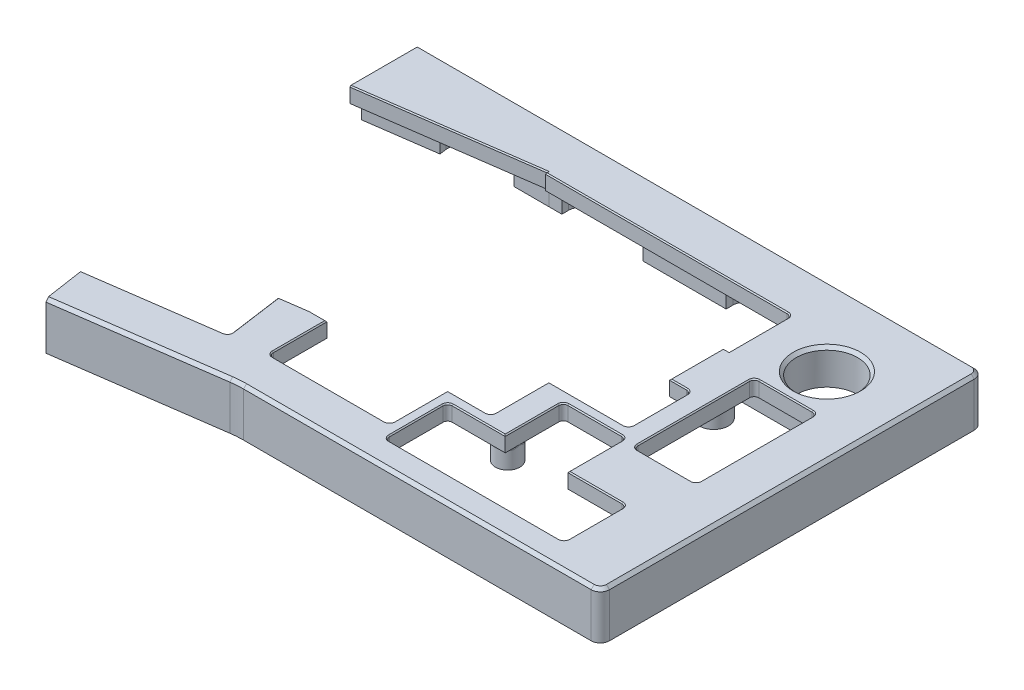
SolidWorks part; units mm, degrees
ref_plane "Front Plane" through (0, 0, 0) normal (0, 0, 1) x (1, 0, 0)
ref_plane "Top Plane" through (0, 0, 0) normal (0, 1, 0) x (1, 0, 0)
ref_plane "Right Plane" through (0, 0, 0) normal (1, 0, 0) x (0, 0, -1)
sketch "Sketch1" plane through (0, 7, 0) normal (0, 1, 0) x (1, 0, 0)
  line L0 (163.7923, 108.4551) -> (345.2139, 108.4551)
  line L1 (348.2139, 105.4551) -> (348.2139, -13.9968)
  line L2 (345.2139, -16.9968) -> (231.3639, -16.9968)
  line L3 (227.1887, -17.2887) -> (174.3706, -24.7118)
  line L4 (158.5745, -26.9318) -> (229.2661, -16.9968) construction
  line L5 (174.3706, -24.7118) -> (163.7923, 45.7292)
  line L6 (163.7923, 45.7292) -> (163.7923, 108.4551)
  line L7 (-20.6294, 108.4551) -> (-20.6294, -16.9968) construction
  line L12 (333.2139, 68.8908) -> (312.7139, 68.8908)
  line L13 (333.2139, 29.3396) -> (333.2139, 68.8908)
  line L14 (312.7139, 29.3396) -> (333.2139, 29.3396)
  line L15 (312.7139, 68.8908) -> (312.7139, 29.3396)
  line L16 (333.2139, 68.8908) -> (312.7139, 68.8908)
  line L17 (333.2139, 29.3396) -> (333.2139, 68.8908)
  line L18 (312.7139, 29.3396) -> (333.2139, 29.3396)
  line L19 (312.7139, 68.8908) -> (312.7139, 29.3396)
  line L24 (308.8285, 11.7372) -> (308.8285, 30.7884)
  line L25 (308.8285, 30.7884) -> (288.3285, 30.7884)
  line L26 (288.3285, 30.7884) -> (288.3285, 11.7372)
  line L27 (288.3285, 11.7372) -> (269.4673, 11.7372)
  line L28 (269.4673, 11.7372) -> (269.4673, -8.7628)
  line L29 (269.4673, -8.7628) -> (328.0696, -8.7628)
  line L30 (328.0696, -8.7628) -> (328.0696, 11.7372)
  line L31 (328.0696, 11.7372) -> (308.8285, 11.7372)
  line L32 (308.8285, 11.7372) -> (308.8285, 30.7884)
  line L33 (308.8285, 30.7884) -> (288.3285, 30.7884)
  line L34 (288.3285, 30.7884) -> (288.3285, 11.7372)
  line L35 (288.3285, 11.7372) -> (269.4673, 11.7372)
  line L36 (269.4673, 11.7372) -> (269.4673, -8.7628)
  line L37 (269.4673, -8.7628) -> (328.0696, -8.7628)
  line L38 (328.0696, -8.7628) -> (328.0696, 11.7372)
  line L39 (328.0696, 11.7372) -> (308.8285, 11.7372)
  line L59 (220.4901, 92.7047) -> (220.3983, 93.3575)
  line L60 (220.3983, 93.3575) -> (143.4989, 82.55)
  line L61 (143.4989, 82.55) -> (146.1495, 63.6897)
  line L62 (146.1495, 63.6897) -> (136.7192, 62.3644)
  line L63 (136.7192, 62.3644) -> (139.5722, 42.0639)
  line L64 (139.5722, 42.0639) -> (144.2882, 42.7267)
  line L65 (144.2882, 42.7267) -> (146.738, 25.2953)
  line L66 (146.738, 25.2953) -> (137.3043, 23.9695)
  line L67 (137.3043, 23.9695) -> (140.1573, 3.669)
  line L68 (140.1573, 3.669) -> (149.2141, 4.9418)
  line L69 (149.2141, 4.9418) -> (151.8663, -13.9296)
  line L70 (151.8663, -13.9296) -> (214.6125, -5.1112)
  line L71 (214.6125, -5.1112) -> (211.9605, 13.7588)
  line L72 (211.9605, 13.7588) -> (221.1558, 15.0512)
  line L73 (221.1558, 15.0512) -> (226.6027, 15.0512)
  line L74 (226.6027, 15.0512) -> (226.6027, -4)
  line L75 (226.6027, -4) -> (266.1519, -4)
  line L76 (266.1519, -4) -> (266.1519, 15.0512)
  line L77 (266.1519, 15.0512) -> (280.2517, 15.0512)
  line L78 (280.2517, 15.0512) -> (280.2517, 34.1024)
  line L79 (280.2517, 34.1024) -> (306.3508, 34.1024)
  line L80 (306.3508, 34.1024) -> (306.3508, 54.6024)
  line L81 (306.3508, 54.6024) -> (299.3029, 54.6024)
  line L82 (299.3029, 54.6024) -> (299.3029, 72.2047)
  line L83 (299.3029, 72.2047) -> (301.207, 72.2047)
  line L84 (301.207, 72.2047) -> (301.207, 92.7047)
  line L85 (301.207, 92.7047) -> (220.4901, 92.7047)
  line L86 (220.4901, 92.7047) -> (220.3983, 93.3575)
  line L87 (220.3983, 93.3575) -> (143.4989, 82.55)
  line L88 (143.4989, 82.55) -> (146.1495, 63.6897)
  line L89 (146.1495, 63.6897) -> (136.7192, 62.3644)
  line L90 (136.7192, 62.3644) -> (139.5722, 42.0639)
  line L91 (139.5722, 42.0639) -> (144.2882, 42.7267)
  line L92 (144.2882, 42.7267) -> (146.738, 25.2953)
  line L93 (146.738, 25.2953) -> (137.3043, 23.9695)
  line L94 (137.3043, 23.9695) -> (140.1573, 3.669)
  line L95 (140.1573, 3.669) -> (149.2141, 4.9418)
  line L96 (149.2141, 4.9418) -> (151.8663, -13.9296)
  line L97 (151.8663, -13.9296) -> (214.6125, -5.1112)
  line L98 (214.6125, -5.1112) -> (211.9605, 13.7588)
  line L99 (211.9605, 13.7588) -> (221.1558, 15.0512)
  line L100 (221.1558, 15.0512) -> (226.6027, 15.0512)
  line L101 (226.6027, 15.0512) -> (226.6027, -4)
  line L102 (226.6027, -4) -> (266.1519, -4)
  line L103 (266.1519, -4) -> (266.1519, 15.0512)
  line L104 (266.1519, 15.0512) -> (280.2517, 15.0512)
  line L105 (280.2517, 15.0512) -> (280.2517, 34.1024)
  line L106 (280.2517, 34.1024) -> (306.3508, 34.1024)
  line L107 (306.3508, 34.1024) -> (306.3508, 54.6024)
  line L108 (306.3508, 54.6024) -> (299.3029, 54.6024)
  line L109 (299.3029, 54.6024) -> (299.3029, 72.2047)
  line L110 (299.3029, 72.2047) -> (301.207, 72.2047)
  line L111 (301.207, 72.2047) -> (301.207, 92.7047)
  line L112 (301.207, 92.7047) -> (220.4901, 92.7047)
  arc A0 (348.2139, -13.9968) -> (345.2139, -16.9968) centre (345.2139, -13.9968) cw
  circle A1 centre (322.9639, 82.4547) radius 3.45
  circle A2 centre (322.9639, 82.4547) radius 3.45
  arc A3 (348.2139, 105.4551) -> (345.2139, 108.4551) centre (345.2139, 105.4551) ccw
  arc A4 (227.1887, -17.2887) -> (231.3639, -16.9968) centre (231.3639, -46.9968) cw
  point P4 (-20.6294, 45.7292)
  point P42 (348.2139, -16.9968)
  point P48 (348.2139, 108.4551)
  point P54 (229.2661, -16.9968)
  dimension "D5" = 3
  dimension "D6" = 30
  dimension "D1" = 0
  dimension "D2" = 0
  dimension "D3" = 0
  dimension "D4" = 0
extrude "Boss-Extrude1" add sketch "Sketch1" against normal offset from surface (5 mm away) 1 contours L3 A4 L2 A0 L1 A3 L0 L6 L87 L86 L112 L111 L110 L109 L108 L107 L106 L105 L104 L103 L102 L101 L100 L99 L98 L97 L5 L19 L16 L17 L18 L39 L38 L37 L36 L35 L34 L33 L32 A2 region at (254.5031, 7, -106.1803)
fillet "Fillet1" radius 1 7 edges at (200.7796, 7, 21.0003) (229.2712, 7, 17.0698) (288.2889, 7, 16.9968) (347.3353, 7, 16.1181) (348.2139, 7, -45.7292) (347.3353, 7, -107.5764) (254.5031, 7, -108.4551) profile chamfer
fillet "Fillet2" radius 1.5 17 edges at (301.207, 4.5, -92.7047) (312.7139, 4.5, -29.3396) (333.2139, 4.5, -29.3396) (333.2139, 4.5, -68.8908) (312.7139, 4.5, -68.8908) (306.3508, 4.5, -54.6024) (306.3508, 4.5, -34.1024) (280.2517, 4.5, -15.0512) (266.1519, 4.5, 4) (226.6027, 4.5, 4) (214.6125, 4.5, 5.1112) (269.4673, 4.5, 8.7628) (328.0696, 4.5, 8.7628) (328.0696, 4.5, -11.7372) (308.8285, 4.5, -30.7884) (288.3285, 4.5, -30.7884) (269.4673, 4.5, -11.7372)
sketch "Sketch2" plane through (0, 7, 0) normal (0, 1, 0) x (1, 0, 0)
  circle A1 centre (322.9639, 82.4547) radius 10.025
  circle A2 centre (322.9639, 82.4547) radius 10.025
  dimension "D1" = 0
extrude "Cut-Extrude1" cut sketch "Sketch2" against normal through all
chamfer "Chamfer1" distance 1 angle 45 1 edges at (322.9639, 7, -72.4297)
chamfer "Chamfer2" distance 0.35 angle 45 47 edges at (322.9639, 7, -29.3396) (332.7746, 7, -29.779) (313.1533, 7, -29.779) (333.2139, 7, -49.1152) (312.7139, 7, -49.1152) (332.7746, 7, -68.4514) (313.1533, 7, -68.4514) (322.9639, 7, -68.8908) (288.3285, 7, -20.5128) (288.7678, 7, -30.349) (298.5785, 7, -30.7884) (308.3891, 7, -30.349) (308.8285, 7, -20.5128) (279.6479, 7, -11.7372) (317.699, 7, -11.7372) (269.9066, 7, -11.2979) (327.6303, 7, -11.2979) (269.4673, 7, -1.4872) (328.0696, 7, -1.4872) (269.9066, 7, 8.3234) (327.6303, 7, 8.3234) (298.7685, 7, 8.7628) (192.7234, 7, 8.1876) (214.1163, 7, 4.7373) (213.1821, 7, -5.0665) (223.8793, 7, -15.0512) (216.5581, 7, -14.405) (226.6027, 7, -6.2756) (227.042, 7, 3.5607) (246.3773, 7, 4) (265.7125, 7, 3.5607) (266.1519, 7, -6.2756) (272.4518, 7, -15.0512) (279.8124, 7, -15.4905) (280.2517, 7, -25.3268) (292.5513, 7, -34.1024) (305.9115, 7, -34.5418) (306.3508, 7, -44.3524) (305.9115, 7, -54.1631) (302.0768, 7, -54.6024) (299.3029, 7, -63.4036) (300.2549, 7, -72.2047) (301.207, 7, -81.7047) (300.7676, 7, -92.2654) (260.0985, 7, -92.7047) (220.4442, 7, -93.0311) (192.0953, 7, -89.3798)
sketch "Sketch3" plane through (0, 2, 0) normal (0, -1, 0) x (1, 0, 0)
  line L0 (191.9476, 10.8212) -> (192.2607, 13.0493)
  line L1 (189.0691, 17.2847) -> (175.2054, 19.2331)
  line L9 (163.7923, -89.1482) -> (186.3819, -92.3229)
  line L10 (186.3819, -92.3229) -> (186.0687, -94.551)
  line L11 (189.2603, -98.7864) -> (203.1241, -100.7349)
  line L12 (207.3595, -97.5433) -> (207.6864, -95.2174)
  line L13 (207.6864, -95.2174) -> (219.1545, -95.2047)
  line L14 (219.1545, -95.2047) -> (223.4041, -95.2047)
  line L15 (223.4041, -95.2047) -> (223.4041, -97.4547)
  line L16 (227.1541, -101.2047) -> (246.1541, -101.2047)
  line L17 (249.9041, -97.4547) -> (249.9041, -95.2047)
  line L18 (249.9041, -95.2047) -> (277.207, -95.2047)
  line L19 (277.207, -95.2047) -> (277.207, -97.4547)
  line L20 (280.957, -101.2047) -> (299.957, -101.2047)
  line L21 (303.707, -97.4547) -> (303.707, -71.3908)
  line L22 (303.707, -71.3908) -> (330.2746, -71.3908)
  line L23 (330.2746, -71.3908) -> (335.2746, -66.3908)
  line L24 (174.3706, 24.7118) -> (172.3197, 11.0551)
  line L25 (172.3197, 11.0551) -> (213.1271, 5.32)
  line L26 (214.4037, 3.6258) -> (211.9605, -13.7588)
  line L27 (211.9605, -13.7588) -> (221.1558, -15.0512)
  line L28 (221.1558, -15.0512) -> (226.6027, -15.0512)
  line L29 (226.6027, -15.0512) -> (226.6027, 2.5)
  line L30 (228.1027, 4) -> (264.6519, 4)
  line L31 (266.1519, 2.5) -> (266.1519, -15.0512)
  line L32 (266.1519, -15.0512) -> (278.7517, -15.0512)
  line L33 (280.2517, -16.5512) -> (280.2517, -34.1024)
  line L34 (280.2517, -34.1024) -> (304.8508, -34.1024)
  line L35 (306.3508, -35.6024) -> (306.3508, -53.1024)
  line L36 (304.8508, -54.6024) -> (299.3029, -54.6024)
  line L37 (299.3029, -54.6024) -> (299.3029, -72.2047)
  line L38 (299.3029, -72.2047) -> (301.207, -72.2047)
  line L39 (301.207, -72.2047) -> (301.207, -91.2047)
  line L40 (299.707, -92.7047) -> (220.4901, -92.7047)
  line L41 (220.4901, -92.7047) -> (220.3983, -93.3575)
  line L42 (220.3983, -93.3575) -> (163.7923, -85.402)
  line L43 (163.7923, -85.402) -> (163.7923, -108.4551)
  line L44 (163.7923, -108.4551) -> (345.2139, -108.4551)
  line L45 (348.2139, -105.4551) -> (348.2139, 13.9968)
  line L46 (345.2139, 16.9968) -> (231.3639, 16.9968)
  line L47 (227.1887, 17.2887) -> (174.3706, 24.7118)
  line L68 (163.7923, -108.4551) -> (345.2139, -108.4551)
  line L69 (348.2139, -105.4551) -> (348.2139, 13.9968)
  line L70 (345.2139, 16.9968) -> (231.3639, 16.9968)
  line L71 (227.1887, 17.2887) -> (174.3706, 24.7118)
  line L72 (335.2746, -66.3908) -> (337.9639, -66.3908)
  line L73 (341.7139, -62.6408) -> (341.7139, -48.6408)
  line L74 (337.9639, -44.8908) -> (335.7139, -44.8908)
  line L75 (335.7139, -44.8908) -> (335.7139, -24.2372)
  line L76 (335.7139, -24.2372) -> (337.9639, -24.2372)
  line L77 (341.7139, -20.4872) -> (341.7139, -6.4872)
  line L78 (337.9639, -2.7372) -> (335.7139, -2.7372)
  line L79 (335.7139, -2.7372) -> (335.7139, 3.8234)
  line L80 (335.7139, 3.8234) -> (330.2746, 9.2628)
  line L81 (330.2746, 9.2628) -> (323.7139, 9.2628)
  line L82 (323.7139, 9.2628) -> (323.7139, 11.5128)
  line L83 (319.9639, 15.2628) -> (300.9639, 15.2628)
  line L84 (297.2139, 11.5128) -> (297.2139, 9.2628)
  line L85 (297.2139, 9.2628) -> (263.7139, 9.2628)
  line L86 (263.7139, 9.2628) -> (263.7139, 11.5128)
  line L87 (259.9639, 15.2628) -> (240.9639, 15.2628)
  line L88 (237.2139, 11.5128) -> (237.2139, 9.2628)
  line L89 (237.2139, 9.2628) -> (203.0362, 9.2628)
  line L90 (203.0362, 9.2628) -> (191.9476, 10.8212)
  line L91 (136.5182, 13.8474) -> (136.5182, -32.8206)
  line L92 (136.5182, -43.3206) -> (136.5182, -90.6166)
  line L93 (136.5182, -90.6166) -> (158.3041, -93.6785)
  line L94 (161.6924, -91.1252) -> (162.1099, -88.1544)
  line L95 (162.1099, -88.1544) -> (187.229, -91.6846)
  line L96 (187.229, -91.6846) -> (186.8114, -94.6554)
  line L97 (189.3647, -98.0437) -> (203.2285, -99.9922)
  line L98 (206.6168, -97.4389) -> (207.0343, -94.4681)
  line L99 (207.0343, -94.4681) -> (219.1541, -94.4547)
  line L100 (219.1541, -94.4547) -> (224.1541, -94.4547)
  line L101 (224.1541, -94.4547) -> (224.1541, -97.4547)
  line L102 (227.1541, -100.4547) -> (246.1541, -100.4547)
  line L103 (249.1541, -97.4547) -> (249.1541, -94.4547)
  line L104 (249.1541, -94.4547) -> (277.957, -94.4547)
  line L105 (277.957, -94.4547) -> (277.957, -97.4547)
  line L106 (280.957, -100.4547) -> (299.957, -100.4547)
  line L107 (302.957, -97.4547) -> (302.957, -70.6408)
  line L108 (302.957, -70.6408) -> (329.9639, -70.6408)
  line L109 (329.9639, -70.6408) -> (334.9639, -65.6408)
  line L110 (334.9639, -65.6408) -> (337.9639, -65.6408)
  line L111 (340.9639, -62.6408) -> (340.9639, -48.6408)
  line L112 (337.9639, -45.6408) -> (334.9639, -45.6408)
  line L113 (334.9639, -45.6408) -> (334.9639, -23.4872)
  line L114 (334.9639, -23.4872) -> (337.9639, -23.4872)
  line L115 (340.9639, -20.4872) -> (340.9639, -6.4872)
  line L116 (337.9639, -3.4872) -> (334.9639, -3.4872)
  line L117 (334.9639, -3.4872) -> (334.9639, 3.5128)
  line L118 (334.9639, 3.5128) -> (329.9639, 8.5128)
  line L119 (329.9639, 8.5128) -> (322.9639, 8.5128)
  line L120 (322.9639, 8.5128) -> (322.9639, 11.5128)
  line L121 (319.9639, 14.5128) -> (300.9639, 14.5128)
  line L122 (297.9639, 11.5128) -> (297.9639, 8.5128)
  line L123 (297.9639, 8.5128) -> (262.9639, 8.5128)
  line L124 (262.9639, 8.5128) -> (262.9639, 11.5128)
  line L125 (259.9639, 14.5128) -> (240.9639, 14.5128)
  line L126 (237.9639, 11.5128) -> (237.9639, 8.5128)
  line L127 (237.9639, 8.5128) -> (202.9837, 8.5128)
  line L128 (202.9837, 8.5128) -> (191.1005, 10.1828)
  line L129 (191.1005, 10.1828) -> (191.518, 13.1536)
  line L130 (188.9647, 16.542) -> (175.101, 18.4904)
  line L131 (171.7127, 15.9371) -> (171.2951, 12.9663)
  line L132 (171.2951, 12.9663) -> (165.0257, 13.8474)
  line L133 (165.0257, 13.8474) -> (136.5182, 13.8474)
  line L137 (161.6924, -91.1252) -> (162.1099, -88.1544) construction
  line L138 (162.1099, -88.1544) -> (187.229, -91.6846) construction
  line L139 (187.229, -91.6846) -> (186.8114, -94.6554) construction
  line L140 (189.3647, -98.0437) -> (203.2285, -99.9922) construction
  line L141 (206.6168, -97.4389) -> (207.0343, -94.4681) construction
  line L142 (207.0343, -94.4681) -> (219.1541, -94.4547) construction
  line L143 (219.1541, -94.4547) -> (224.1541, -94.4547) construction
  line L144 (224.1541, -94.4547) -> (224.1541, -97.4547) construction
  line L145 (227.1541, -100.4547) -> (246.1541, -100.4547) construction
  line L146 (249.1541, -97.4547) -> (249.1541, -94.4547) construction
  line L147 (249.1541, -94.4547) -> (277.957, -94.4547) construction
  line L148 (277.957, -94.4547) -> (277.957, -97.4547) construction
  line L149 (280.957, -100.4547) -> (299.957, -100.4547) construction
  line L150 (302.957, -97.4547) -> (302.957, -70.6408) construction
  line L151 (302.957, -70.6408) -> (329.9639, -70.6408) construction
  line L152 (329.9639, -70.6408) -> (334.9639, -65.6408) construction
  line L153 (334.9639, -65.6408) -> (337.9639, -65.6408) construction
  line L154 (340.9639, -62.6408) -> (340.9639, -48.6408) construction
  line L155 (337.9639, -45.6408) -> (334.9639, -45.6408) construction
  line L156 (334.9639, -45.6408) -> (334.9639, -23.4872) construction
  line L157 (334.9639, -23.4872) -> (337.9639, -23.4872) construction
  line L158 (340.9639, -20.4872) -> (340.9639, -6.4872) construction
  line L159 (337.9639, -3.4872) -> (334.9639, -3.4872) construction
  line L160 (334.9639, -3.4872) -> (334.9639, 3.5128) construction
  line L161 (334.9639, 3.5128) -> (329.9639, 8.5128) construction
  line L162 (329.9639, 8.5128) -> (322.9639, 8.5128) construction
  line L163 (322.9639, 8.5128) -> (322.9639, 11.5128) construction
  line L164 (319.9639, 14.5128) -> (300.9639, 14.5128) construction
  line L165 (297.9639, 11.5128) -> (297.9639, 8.5128) construction
  line L166 (297.9639, 8.5128) -> (262.9639, 8.5128) construction
  line L167 (262.9639, 8.5128) -> (262.9639, 11.5128) construction
  line L168 (259.9639, 14.5128) -> (240.9639, 14.5128) construction
  line L169 (237.9639, 11.5128) -> (237.9639, 8.5128) construction
  line L170 (237.9639, 8.5128) -> (202.9837, 8.5128) construction
  line L171 (202.9837, 8.5128) -> (191.1005, 10.1828) construction
  line L172 (191.1005, 10.1828) -> (191.518, 13.1536)
  line L173 (188.9647, 16.542) -> (175.101, 18.4904) construction
  line L174 (171.7127, 15.9371) -> (171.2951, 12.9663) construction
  line L175 (171.2951, 12.9663) -> (165.0257, 13.8474) construction
  line L177 (165.0782, 14.5974) -> (135.7682, 14.5974) construction
  line L178 (135.7682, 14.5974) -> (135.7682, -33.6335) construction
  line L179 (135.7682, -42.5076) -> (135.7682, -91.2686) construction
  line L180 (135.7682, -91.2686) -> (158.1997, -94.4212) construction
  line L181 (136.5182, 13.8474) -> (136.5182, -32.8206) construction
  line L182 (136.5182, -43.3206) -> (136.5182, -90.6166) construction
  line L183 (136.5182, -90.6166) -> (158.3041, -93.6785) construction
  line L184 (165.0257, 13.8474) -> (136.5182, 13.8474) construction
  line L185 (163.7923, -108.4551) -> (163.7923, -89.1482)
  line L186 (163.7923, -108.4551) -> (163.7923, -85.402) construction
  line L187 (174.3706, 24.7118) -> (173.5258, 19.0864)
  line L188 (162.4351, -91.2296) -> (162.7483, -89.0014) construction
  line L189 (162.7483, -89.0014) -> (186.3819, -92.3229) construction
  line L190 (172.3197, 11.0551) -> (174.3706, 24.7118) construction
  line L192 (170.97, 16.0415) -> (170.6568, 13.8134) construction
  line L193 (170.6568, 13.8134) -> (165.0782, 14.5974) construction
  arc A0 (192.2607, 13.0493) -> (189.0691, 17.2847) centre (188.5472, 13.5712) ccw
  arc A1 (175.2054, 19.2331) -> (173.5258, 19.0864) centre (174.6835, 15.5196) ccw
  arc A4 (186.0687, -94.551) -> (189.2603, -98.7864) centre (189.7822, -95.0729) ccw
  arc A5 (203.1241, -100.7349) -> (207.3595, -97.5433) centre (203.646, -97.0214) ccw
  arc A6 (223.4041, -97.4547) -> (227.1541, -101.2047) centre (227.1541, -97.4547) ccw
  arc A7 (246.1541, -101.2047) -> (249.9041, -97.4547) centre (246.1541, -97.4547) ccw
  arc A8 (277.207, -97.4547) -> (280.957, -101.2047) centre (280.957, -97.4547) ccw
  arc A9 (299.957, -101.2047) -> (303.707, -97.4547) centre (299.957, -97.4547) ccw
  arc A10 (214.4037, 3.6258) -> (213.1271, 5.32) centre (212.9183, 3.8346) ccw
  arc A11 (228.1027, 4) -> (226.6027, 2.5) centre (228.1027, 2.5) ccw
  arc A12 (266.1519, 2.5) -> (264.6519, 4) centre (264.6519, 2.5) ccw
  arc A13 (280.2517, -16.5512) -> (278.7517, -15.0512) centre (278.7517, -16.5512) ccw
  arc A14 (306.3508, -35.6024) -> (304.8508, -34.1024) centre (304.8508, -35.6024) ccw
  arc A15 (304.8508, -54.6024) -> (306.3508, -53.1024) centre (304.8508, -53.1024) ccw
  arc A16 (299.707, -92.7047) -> (301.207, -91.2047) centre (299.707, -91.2047) ccw
  arc A17 (345.2139, -108.4551) -> (348.2139, -105.4551) centre (345.2139, -105.4551) ccw
  arc A18 (348.2139, 13.9968) -> (345.2139, 16.9968) centre (345.2139, 13.9968) ccw
  arc A19 (227.1887, 17.2887) -> (231.3639, 16.9968) centre (231.3639, 46.9968) ccw
  arc A27 (345.2139, -108.4551) -> (348.2139, -105.4551) centre (345.2139, -105.4551) ccw
  arc A28 (348.2139, 13.9968) -> (345.2139, 16.9968) centre (345.2139, 13.9968) ccw
  arc A29 (227.1887, 17.2887) -> (231.3639, 16.9968) centre (231.3639, 46.9968) ccw
  arc A30 (337.9639, -66.3908) -> (341.7139, -62.6408) centre (337.9639, -62.6408) ccw
  arc A31 (341.7139, -48.6408) -> (337.9639, -44.8908) centre (337.9639, -48.6408) ccw
  arc A32 (337.9639, -24.2372) -> (341.7139, -20.4872) centre (337.9639, -20.4872) ccw
  arc A33 (341.7139, -6.4872) -> (337.9639, -2.7372) centre (337.9639, -6.4872) ccw
  arc A34 (323.7139, 11.5128) -> (319.9639, 15.2628) centre (319.9639, 11.5128) ccw
  arc A35 (300.9639, 15.2628) -> (297.2139, 11.5128) centre (300.9639, 11.5128) ccw
  arc A36 (263.7139, 11.5128) -> (259.9639, 15.2628) centre (259.9639, 11.5128) ccw
  arc A37 (240.9639, 15.2628) -> (237.2139, 11.5128) centre (240.9639, 11.5128) ccw
  arc A38 (136.5182, -43.3206) -> (136.5182, -32.8206) centre (136.5182, -38.0706) ccw
  arc A39 (158.3041, -93.6785) -> (161.6924, -91.1252) centre (158.7216, -90.7077) ccw
  arc A40 (186.8114, -94.6554) -> (189.3647, -98.0437) centre (189.7822, -95.0729) ccw
  arc A41 (203.2285, -99.9922) -> (206.6168, -97.4389) centre (203.646, -97.0214) ccw
  arc A42 (224.1541, -97.4547) -> (227.1541, -100.4547) centre (227.1541, -97.4547) ccw
  arc A43 (246.1541, -100.4547) -> (249.1541, -97.4547) centre (246.1541, -97.4547) ccw
  arc A44 (277.957, -97.4547) -> (280.957, -100.4547) centre (280.957, -97.4547) ccw
  arc A45 (299.957, -100.4547) -> (302.957, -97.4547) centre (299.957, -97.4547) ccw
  arc A46 (337.9639, -65.6408) -> (340.9639, -62.6408) centre (337.9639, -62.6408) ccw
  arc A47 (340.9639, -48.6408) -> (337.9639, -45.6408) centre (337.9639, -48.6408) ccw
  arc A48 (337.9639, -23.4872) -> (340.9639, -20.4872) centre (337.9639, -20.4872) ccw
  arc A49 (340.9639, -6.4872) -> (337.9639, -3.4872) centre (337.9639, -6.4872) ccw
  arc A50 (322.9639, 11.5128) -> (319.9639, 14.5128) centre (319.9639, 11.5128) ccw
  arc A51 (300.9639, 14.5128) -> (297.9639, 11.5128) centre (300.9639, 11.5128) ccw
  arc A52 (262.9639, 11.5128) -> (259.9639, 14.5128) centre (259.9639, 11.5128) ccw
  arc A53 (240.9639, 14.5128) -> (237.9639, 11.5128) centre (240.9639, 11.5128) ccw
  arc A54 (191.518, 13.1536) -> (188.9647, 16.542) centre (188.5472, 13.5712) ccw
  arc A55 (175.101, 18.4904) -> (171.7127, 15.9371) centre (174.6835, 15.5196) ccw
  arc A58 (186.8114, -94.6554) -> (189.3647, -98.0437) centre (189.7822, -95.0729) ccw construction
  arc A59 (203.2285, -99.9922) -> (206.6168, -97.4389) centre (203.646, -97.0214) ccw construction
  arc A60 (224.1541, -97.4547) -> (227.1541, -100.4547) centre (227.1541, -97.4547) ccw construction
  arc A61 (246.1541, -100.4547) -> (249.1541, -97.4547) centre (246.1541, -97.4547) ccw construction
  arc A62 (277.957, -97.4547) -> (280.957, -100.4547) centre (280.957, -97.4547) ccw construction
  arc A63 (299.957, -100.4547) -> (302.957, -97.4547) centre (299.957, -97.4547) ccw construction
  arc A64 (337.9639, -65.6408) -> (340.9639, -62.6408) centre (337.9639, -62.6408) ccw construction
  arc A65 (340.9639, -48.6408) -> (337.9639, -45.6408) centre (337.9639, -48.6408) ccw construction
  arc A66 (337.9639, -23.4872) -> (340.9639, -20.4872) centre (337.9639, -20.4872) ccw construction
  arc A67 (340.9639, -6.4872) -> (337.9639, -3.4872) centre (337.9639, -6.4872) ccw construction
  arc A68 (322.9639, 11.5128) -> (319.9639, 14.5128) centre (319.9639, 11.5128) ccw construction
  arc A69 (300.9639, 14.5128) -> (297.9639, 11.5128) centre (300.9639, 11.5128) ccw construction
  arc A70 (262.9639, 11.5128) -> (259.9639, 14.5128) centre (259.9639, 11.5128) ccw construction
  arc A71 (240.9639, 14.5128) -> (237.9639, 11.5128) centre (240.9639, 11.5128) ccw construction
  arc A72 (191.518, 13.1536) -> (188.9647, 16.542) centre (188.5472, 13.5712) ccw construction
  arc A73 (175.101, 18.4904) -> (171.7127, 15.9371) centre (174.6835, 15.5196) ccw construction
  arc A74 (135.7682, -42.5076) -> (135.7682, -33.6335) centre (136.5182, -38.0706) ccw construction
  arc A75 (158.1997, -94.4212) -> (162.4351, -91.2296) centre (158.7216, -90.7077) ccw construction
  arc A76 (136.5182, -43.3206) -> (136.5182, -32.8206) centre (136.5182, -38.0706) ccw construction
  arc A77 (158.3041, -93.6785) -> (161.6924, -91.1252) centre (158.7216, -90.7077) ccw construction
  circle A78 centre (322.9639, -82.4547) radius 10.025
  arc A79 (175.2054, 19.2331) -> (170.97, 16.0415) centre (174.6835, 15.5196) ccw construction
  dimension "D1" = 0
  dimension "D2" = 0
  dimension "D3" = 0.75
extrude "Boss-Extrude2" add sketch "Sketch3" along normal up to surface (6.5 mm away) contours A37 L87 A36 L86 L85 L84 A35 L83 A34 L82 L81 L80 L79 L78 A33 L77 A32 L76 L75 L74 A31 L73 A30 L72 L23 L22 L21 A9 L20 A8 L19 L18 L17 A7 L16 A6 L15 L14 L13 L12 A5 L11 A4 L10 L9 L185 L68 A27 L69 A28 L70 region at (194.3568, 2, 11.6186)
sketch "Sketch4" plane through (0, -4.5, 0) normal (0, -1, 0) x (1, 0, 0)
  line L0 (163.7923, -104.4551) -> (344.2139, -104.4551)
  line L1 (344.2139, -104.4551) -> (344.2139, 12.9968)
  line L2 (344.2139, 12.9968) -> (231.3639, 12.9968)
  line L3 (226.632, 13.3276) -> (173.8139, 20.7507)
  line L5 (163.7923, -104.4551) -> (163.7923, -108.4551)
  line L6 (174.3706, 24.7118) -> (173.7765, 20.756)
  line L7 (174.3706, 24.7118) -> (173.5258, 19.0864) construction
  line L8 (173.8139, 20.7507) -> (173.7765, 20.756)
  line L42 (240.9639, 15.2628) -> (259.9639, 15.2628)
  line L43 (263.7139, 11.5128) -> (263.7139, 9.2628)
  line L44 (263.7139, 9.2628) -> (297.2139, 9.2628)
  line L45 (297.2139, 9.2628) -> (297.2139, 11.5128)
  line L46 (300.9639, 15.2628) -> (319.9639, 15.2628)
  line L47 (323.7139, 11.5128) -> (323.7139, 9.2628)
  line L48 (323.7139, 9.2628) -> (330.2746, 9.2628)
  line L49 (330.2746, 9.2628) -> (335.7139, 3.8234)
  line L50 (335.7139, 3.8234) -> (335.7139, -2.7372)
  line L51 (335.7139, -2.7372) -> (337.9639, -2.7372)
  line L52 (341.7139, -6.4872) -> (341.7139, -20.4872)
  line L53 (337.9639, -24.2372) -> (335.7139, -24.2372)
  line L54 (335.7139, -24.2372) -> (335.7139, -44.8908)
  line L55 (335.7139, -44.8908) -> (337.9639, -44.8908)
  line L56 (341.7139, -48.6408) -> (341.7139, -62.6408)
  line L57 (337.9639, -66.3908) -> (335.2746, -66.3908)
  line L58 (335.2746, -66.3908) -> (330.2746, -71.3908)
  line L59 (330.2746, -71.3908) -> (303.707, -71.3908)
  line L60 (303.707, -71.3908) -> (303.707, -97.4547)
  line L61 (299.957, -101.2047) -> (280.957, -101.2047)
  line L62 (277.207, -97.4547) -> (277.207, -95.2047)
  line L63 (277.207, -95.2047) -> (249.9041, -95.2047)
  line L64 (249.9041, -95.2047) -> (249.9041, -97.4547)
  line L65 (246.1541, -101.2047) -> (227.1541, -101.2047)
  line L66 (223.4041, -97.4547) -> (223.4041, -95.2047)
  line L67 (223.4041, -95.2047) -> (219.1545, -95.2047)
  line L68 (219.1545, -95.2047) -> (207.6864, -95.2174)
  line L69 (207.6864, -95.2174) -> (207.3595, -97.5433)
  line L70 (203.1241, -100.7349) -> (189.2603, -98.7864)
  line L71 (186.0687, -94.551) -> (186.3819, -92.3229)
  line L72 (186.3819, -92.3229) -> (163.7923, -89.1482)
  line L73 (163.7923, -89.1482) -> (163.7923, -108.4551)
  line L74 (163.7923, -108.4551) -> (345.2139, -108.4551)
  line L75 (348.2139, -105.4551) -> (348.2139, 13.9968)
  line L76 (345.2139, 16.9968) -> (231.3639, 16.9968)
  line L77 (227.1887, 17.2887) -> (174.3706, 24.7118)
  line L78 (174.3706, 24.7118) -> (173.5258, 19.0864)
  line L79 (175.2054, 19.2331) -> (189.0691, 17.2847)
  line L80 (192.2607, 13.0493) -> (191.9476, 10.8212)
  line L81 (191.9476, 10.8212) -> (203.0362, 9.2628)
  line L82 (203.0362, 9.2628) -> (237.2139, 9.2628)
  line L83 (237.2139, 9.2628) -> (237.2139, 11.5128)
  line L116 (163.7923, -108.4551) -> (345.2139, -108.4551)
  line L117 (348.2139, -105.4551) -> (348.2139, 13.9968)
  line L118 (345.2139, 16.9968) -> (231.3639, 16.9968)
  line L119 (227.1887, 17.2887) -> (174.3706, 24.7118)
  arc A1 (344.2139, -104.4551) -> (344.2139, -104.4551) centre (344.2139, -104.4551) ccw
  arc A2 (344.2139, 12.9968) -> (344.2139, 12.9968) centre (344.2139, 12.9968) ccw
  arc A3 (226.632, 13.3276) -> (231.3639, 12.9968) centre (231.3639, 46.9968) ccw
  arc A19 (240.9639, 15.2628) -> (237.2139, 11.5128) centre (240.9639, 11.5128) ccw
  arc A20 (263.7139, 11.5128) -> (259.9639, 15.2628) centre (259.9639, 11.5128) ccw
  arc A21 (300.9639, 15.2628) -> (297.2139, 11.5128) centre (300.9639, 11.5128) ccw
  arc A22 (323.7139, 11.5128) -> (319.9639, 15.2628) centre (319.9639, 11.5128) ccw
  arc A23 (341.7139, -6.4872) -> (337.9639, -2.7372) centre (337.9639, -6.4872) ccw
  arc A24 (337.9639, -24.2372) -> (341.7139, -20.4872) centre (337.9639, -20.4872) ccw
  arc A25 (341.7139, -48.6408) -> (337.9639, -44.8908) centre (337.9639, -48.6408) ccw
  arc A26 (337.9639, -66.3908) -> (341.7139, -62.6408) centre (337.9639, -62.6408) ccw
  arc A27 (299.957, -101.2047) -> (303.707, -97.4547) centre (299.957, -97.4547) ccw
  arc A28 (277.207, -97.4547) -> (280.957, -101.2047) centre (280.957, -97.4547) ccw
  arc A29 (246.1541, -101.2047) -> (249.9041, -97.4547) centre (246.1541, -97.4547) ccw
  arc A30 (223.4041, -97.4547) -> (227.1541, -101.2047) centre (227.1541, -97.4547) ccw
  arc A31 (203.1241, -100.7349) -> (207.3595, -97.5433) centre (203.646, -97.0214) ccw
  arc A32 (186.0687, -94.551) -> (189.2603, -98.7864) centre (189.7822, -95.0729) ccw
  arc A33 (345.2139, -108.4551) -> (348.2139, -105.4551) centre (345.2139, -105.4551) ccw
  arc A34 (348.2139, 13.9968) -> (345.2139, 16.9968) centre (345.2139, 13.9968) ccw
  arc A35 (227.1887, 17.2887) -> (231.3639, 16.9968) centre (231.3639, 46.9968) ccw
  arc A36 (175.2054, 19.2331) -> (173.5258, 19.0864) centre (174.6835, 15.5196) ccw
  arc A37 (192.2607, 13.0493) -> (189.0691, 17.2847) centre (188.5472, 13.5712) ccw
  arc A52 (345.2139, -108.4551) -> (348.2139, -105.4551) centre (345.2139, -105.4551) ccw
  arc A53 (348.2139, 13.9968) -> (345.2139, 16.9968) centre (345.2139, 13.9968) ccw
  arc A54 (227.1887, 17.2887) -> (231.3639, 16.9968) centre (231.3639, 46.9968) ccw
  dimension "D1" = 0
  dimension "D2" = 4
extrude "Boss-Extrude3" add sketch "Sketch4" along normal up to surface (4 mm away)
sketch "Sketch6" plane through (0, 2, 0) normal (0, -1, 0) x (-1, 0, 0)
  line L0 (-280.2517, 16.564) -> (-288.3285, 16.564) construction
  circle A0 centre (-306.0084, 62.3908) radius 4.75
  circle A1 centre (-306.0084, 62.3908) radius 5.75 construction
  circle A2 centre (-284.2901, 16.564) radius 4
  dimension "D1" = 1
  dimension "D2" = 8
extrude "Boss-Extrude4" add sketch "Sketch6" along normal up to surface (6.5 mm away) up to face at (322.9639, -4.5, -92.4797)
fillet "Fillet3" radius 1 2 edges at (306.0084, 2, -57.6408) (284.2901, 2, -12.564)
hole_wizard "CSK for M3 Hex Socket Countersunk Cap Screw1" positions "Sketch7" profile "Sketch8" countersink size "M3" standard "ISO"
sketch "Sketch7" plane through (0, -4.5, 0) normal (0, -1, 0) x (-1, 0, 0)
  line L0 (-277.957, 100.2047) -> (-249.1541, 100.2047) construction
  point P0 (-173.8692, 95.6135)
  point P3 (-215.5942, 100.2114)
  point P6 (-263.5556, 100.2047)
  point P10 (-317.3584, 100.2047)
  point P13 (-340.7139, 76.7176)
  point P16 (-306.0084, 62.3908)
  point P19 (-340.7139, 34.564)
  point P22 (-284.2901, 16.564)
  point P25 (-336.5298, -10.0786)
  point P28 (-214.6538, -12.7601)
sketch "Sketch8" plane through (173.8692, -4.5, -95.6135) normal (1, 0, 0) x (0, 0, -1)
  line L0 (0, 0) -> (0, 9.2017)
  line L1 (0, 9.2017) -> (2, 8)
  line L2 (2, 8) -> (2, 0.2)
  line L3 (2, 0.2) -> (2.2, 0)
  line L5 (2.2, 0) -> (0, 0)
  line L6 (-2, 0.2) -> (-2.2, 0) construction
  line L10 (0, 9.2017) -> (-2, 8) construction
  line L11 (0, -6.35) -> (0, 107.95) construction
  dimension "Hole Dia." = 4
  dimension "Hole Depth" = 8
  dimension "Near C'Sink Dia." = 4.4
  dimension "Near C'Sink Angle" = 90
  dimension "Drill Angle" = 118
sketch "Sketch9" plane through (0, -4.5, 0) normal (0, -1, 0) x (1, 0, 0)
  circle A0 centre (214.6538, 12.7601) radius 4
  dimension "D1" = 8
extrude "Cut-Extrude2" cut sketch "Sketch9" along normal through all
